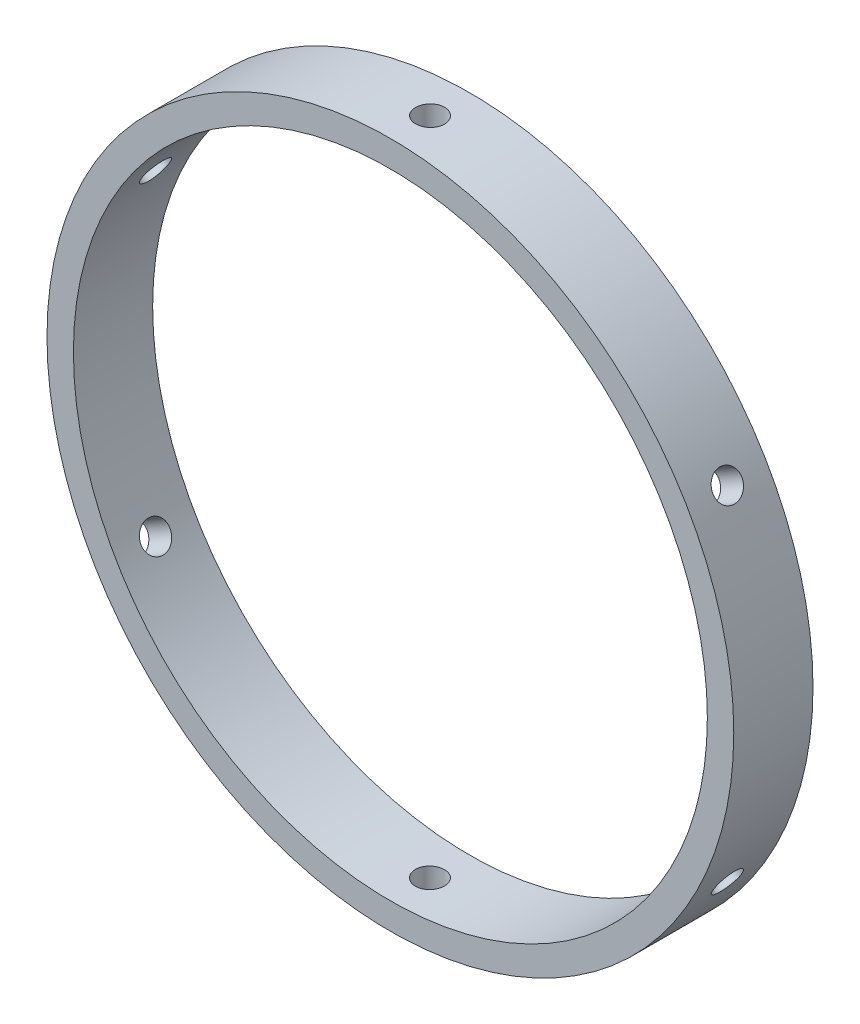
SolidWorks part; units mm, degrees
ref_plane "Front Plane" through (0, 0, 0) normal (0, 0, 1) x (1, 0, 0)
ref_plane "Top Plane" through (0, 0, 0) normal (0, 1, 0) x (1, 0, 0)
ref_plane "Right Plane" through (0, 0, 0) normal (1, 0, 0) x (0, 0, -1)
sketch "Sketch1" plane through (0, 0, 0) normal (0, 0, 1) x (1, 0, 0)
  circle A0 centre (0, 0) radius 76.2
  circle A1 centre (0, 0) radius 82.55
extrude "Boss-Extrude1" add sketch "Sketch1" along normal blind 19.05
sketch "Sketch2" plane through (0, 0, 0) normal (0, 1, 0) x (1, 0, 0)
  line L0 (76.2, 0) -> (-76.2, 0) construction
  line L1 (0, -2.0807) -> (0, -15.8358) construction
  circle A0 centre (0, -9.525) radius 3.4782
  dimension "D1" = 9.525
extrude "Cut-Extrude1" cut sketch "Sketch2" against normal through all
ref_axis "Axis1" through (0, 0, 2.0807) along (0, 0, 1)
pattern_circular "CirPattern1" count 6 over 360 about axis through (0, 0, 2.0807) along (0, 0, 1) of "Cut-Extrude1"
